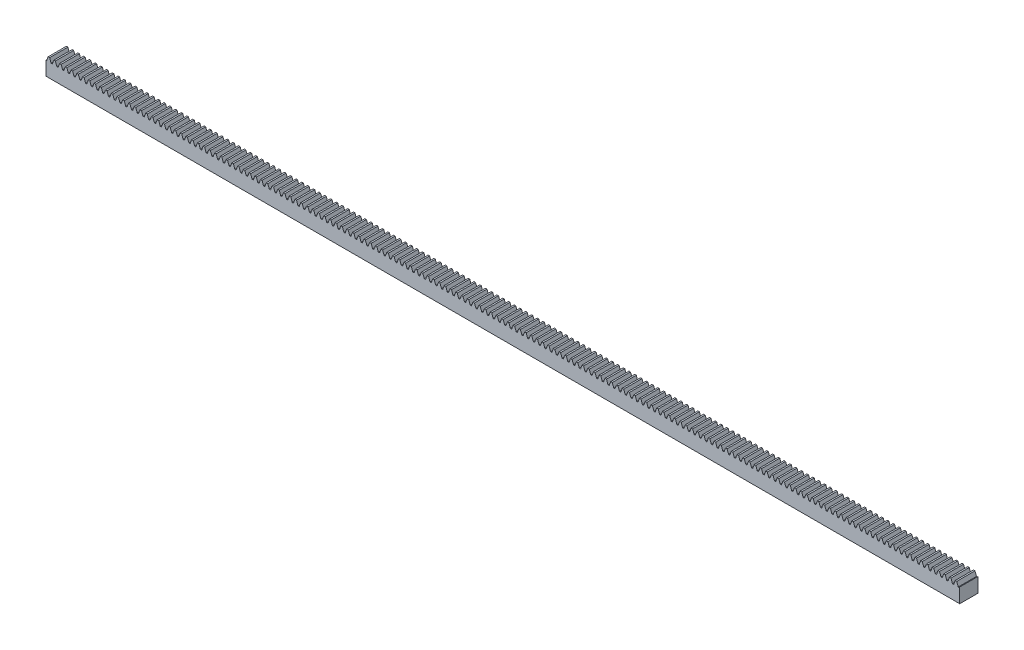
SolidWorks part; units mm, degrees
note: '?' marks a value the reader was unsure of.
ref_plane "Front" through (0, 0, 0) normal (0, 0, 1) x (1, 0, 0)
ref_plane "Top" through (0, 0, 0) normal (0, 1, 0) x (1, 0, 0)
ref_plane "Right" through (0, 0, 0) normal (1, 0, 0) x (0, 0, -1)
sketch "Ritning 1" plane through (0, 0, 0) normal (0, 0, 1) x (1, 0, 0)
  line L1 (-124.1, -4.9) -> (375.9, -4.9)
  line L2 (-124.1, -4.9) -> (-124.1, 4.9)
  line L3 (-124.1, 4.9) -> (375.9, 4.9)
  line L4 (375.9, -4.9) -> (375.9, 4.9)
  dimension "D1" = 500
  dimension "D3" = 4.9
  dimension "D4" = 4.9
extrude "Kuggstångsämne" add sketch "Ritning 1" along normal blind 10
sketch "Ritning 2" plane through (0, 0, 10) normal (0, 0, 1) x (1, 0, 0)
  line L0 (-124.4383, 2.65) -> (-123.7617, 2.65)
  line L1 (-125.2572, 4.9) -> (-124.1, 6.0572)
  line L3 (-124.1, -4.9) -> (375.9, -4.9) construction
  line L4 (375.9, -4.9) -> (375.9, 4.9) construction
  line L7 (-124.1, 6.0572) -> (-122.9428, 4.9)
  line L9 (-122.9428, 4.9) -> (-123.7617, 2.65)
  spline S0 degree 3 poles (-125.2572, 4.9) (-124.9842, 4.15) (-124.7113, 3.4) (-124.4383, 2.65) knots 0 0 0 0 1 1 1 1
  dimension "D1" = 498.8428
  dimension "D2" = 499.6617
  dimension "D3" = 500
  dimension "D4" = 500.3383
  dimension "D5" = 7.55
  dimension "D6" = 9.8
extrude "Kugglucka" cut sketch "Ritning 2" against normal blind 10
ref_axis "Axis" through (375.9, 4.9, 10) along (-1, 0, 0)?
pattern_linear "LPattern" count 160 spacing 3.1416 along (1, 0, 0) of "Kugglucka"
